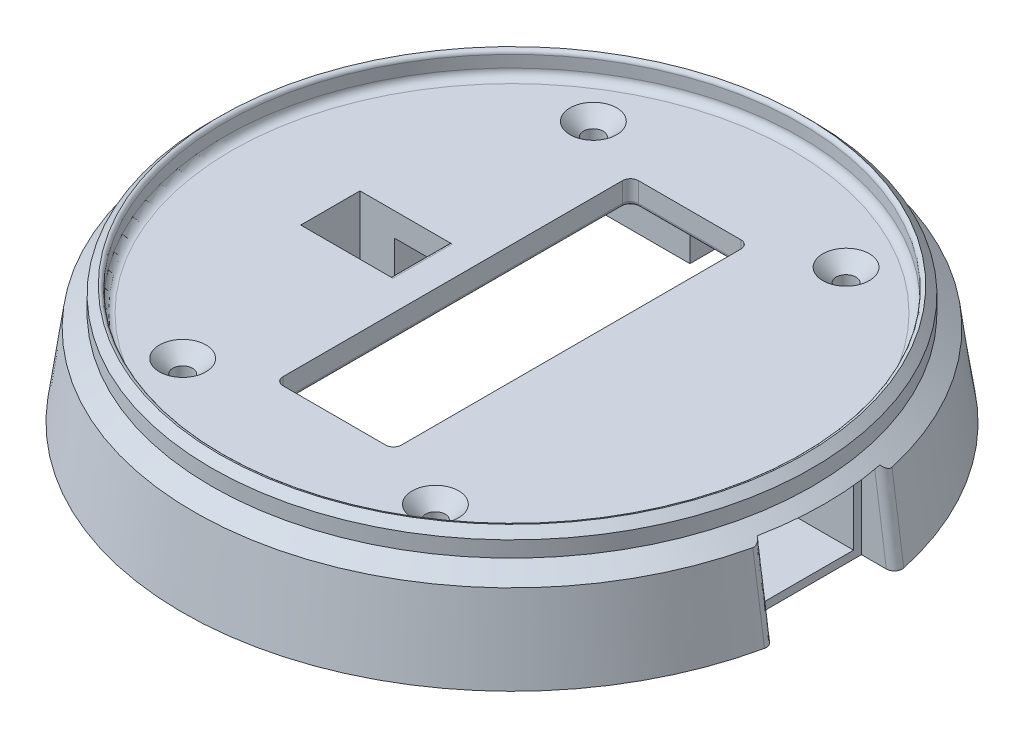
SolidWorks part; units mm, degrees
ref_plane "Front Plane" through (0, 0, 0) normal (0, 0, 1) x (1, 0, 0)
ref_plane "Top Plane" through (0, 0, 0) normal (0, 1, 0) x (1, 0, 0)
ref_plane "Right Plane" through (0, 0, 0) normal (1, 0, 0) x (0, 0, -1)
sketch "Sketch1" plane through (0, 0, 0) normal (0, 1, 0) x (1, 0, 0)
  circle A0 centre (0, 0) radius 41.73
  dimension "D1" = 83.46
extrude "Boss-Extrude1" add sketch "Sketch1" along normal blind 12 draft 8
sketch "Sketch2" plane through (0, 12, 0) normal (0, 1, 0) x (1, 0, 0)
  line L1 (18.65, -28.65) -> (-18.65, -28.65)
  line L2 (18.65, -28.65) -> (18.65, 28.65)
  line L3 (18.65, 28.65) -> (-18.65, 28.65)
  line L4 (-18.65, -28.65) -> (-18.65, 28.65)
  line L5 (18.65, -28.65) -> (-18.65, 28.65) construction
  line L6 (18.65, 28.65) -> (-18.65, -28.65) construction
  point P0 (0, 0)
  dimension "D1" = 37.3
  dimension "D2" = 57.3
extrude "Cut-Extrude1" cut sketch "Sketch2" against normal up to surface (12 mm away) from offset 3 up to face at (0, 0, 41.73) offset against normal yes
sketch "Sketch3" plane through (0, 0, -28.65) normal (0, 0, 1) x (1, 0, 0)
  line L0 (-18.65, 0) -> (18.65, 0) construction
  line L1 (-6.12, 0) -> (6.38, 0)
  line L2 (-6.12, 0) -> (-6.12, 8.5)
  line L3 (-6.12, 8.5) -> (6.38, 8.5)
  line L4 (6.38, 0) -> (6.38, 8.5)
  point P4 (0, 0)
  point P5 (0, 0)
  point P6 (0.13, 8.5)
  dimension "D1" = 12.5
  dimension "D2" = 8.5
  dimension "D3" = 0.13
extrude "Cut-Extrude3" cut sketch "Sketch3" against normal up to surface (12.6288 mm away) up to face at (0, 12, 40.0435)
fillet "Fillet1" radius 2 2 edges at (6.38, 8.5, -34.3401) (-6.12, 8.5, -34.3604)
sketch "Sketch4" plane through (0, 12, 0) normal (0, 1, 0) x (1, 0, 0)
  line L0 (0, 0) -> (0, -22.5) construction
  line L1 (7.5, -22.5) -> (-7.5, -22.5)
  line L2 (7.5, -22.5) -> (7.5, 22.5)
  line L3 (7.5, 22.5) -> (-7.5, 22.5)
  line L4 (-7.5, -22.5) -> (-7.5, 22.5)
  line L5 (0, 0) -> (0, 22.5) construction
  point P4 (0, 0)
  dimension "D1" = 15
  dimension "D2" = 45
extrude "Cut-Extrude4" cut sketch "Sketch4" against normal blind 4.8
fillet "Fillet2" radius 1 4 edges at (7.5, 10.5, -22.5) (-7.5, 10.5, -22.5) (7.5, 10.5, 22.5) (-7.5, 10.5, 22.5)
sketch "Sketch6" plane through (18.65, 0, 0) normal (-1, 0, 0) x (0, 0, 1)
  line L0 (-28.65, 0) -> (28.65, 0) construction
  line L1 (-6.6, 1) -> (6.6, 1)
  line L2 (-6.6, 1) -> (-6.6, 10.2)
  line L3 (-6.6, 10.2) -> (6.6, 10.2)
  line L4 (6.6, 1) -> (6.6, 10.2)
  point P4 (0, 10.2)
  point P7 (0, 0)
  dimension "D1" = 9.2
  dimension "D2" = 13.2
  dimension "D3" = 1
extrude "Cut-Extrude5" cut sketch "Sketch6" against normal up to surface (22.4124 mm away) up to face at (0, 12, 40.0435)
chamfer "Chamfer1" distance 2 angle 70 1 edges at (18.65, 9, 0) first distance on face at (18.65, 9.6, 0)
ref_plane "Plane1" through (41.65, 0, 0) normal (-1, 0, 0) x (0, 0, 1)
sketch "Sketch7" plane through (41.65, 0, 0) normal (-1, 0, 0) x (0, 0, 1)
  line L1 (7.6, 10.7) -> (-7.6, 10.7)
  line L2 (7.6, 10.7) -> (7.6, 0)
  line L3 (7.6, 0) -> (-7.6, 0)
  line L4 (-7.6, 10.7) -> (-7.6, 0)
  line L5 (-41.2788, 0) -> (41.73, 0) construction
  line L7 (-6.6, 1) -> (-6.6, 10.2) construction
  line L8 (6.6, 1) -> (-6.6, 1) construction
  line L9 (-6.6, 1) -> (-6.6, 10.2) construction
  line L10 (6.6, 1) -> (-6.6, 1) construction
  line L11 (6.6, 10.2) -> (-6.6, 10.2)
  line L12 (-6.6, 10.2) -> (-6.6, 1)
  line L13 (-6.6, 1) -> (6.6, 1)
  line L14 (6.6, 1) -> (6.6, 10.2)
  line L15 (6.6, 10.2) -> (-6.6, 10.2) construction
  line L16 (-6.6, 10.2) -> (-6.6, 1) construction
  line L17 (-6.6, 1) -> (6.6, 1) construction
  line L18 (6.6, 1) -> (6.6, 10.2) construction
  point P6 (0, 0)
  point P11 (0, 10.2)
  dimension "D1" = 15.2
  dimension "D2" = 10.7
  dimension "D3" = 0
extrude "Cut-Extrude6" cut sketch "Sketch7" along normal blind 5 and the other way blind 2
fillet "Fillet3" radius 1 3 edges at (40.2262, 10.7, 0)
sketch "Sketch8" plane through (0, 12, 0) normal (0, 1, 0) x (1, 0, 0)
  circle A0 centre (-15.85, 26.15) radius 1.25
  circle A1 centre (-15.85, -25.85) radius 1.25
  circle A2 centre (16.15, 26.15) radius 1.25
  circle A3 centre (16.15, -25.85) radius 1.25
  circle A4 centre (-15.85, 26.15) radius 1.6 construction
  circle A5 centre (16.15, 26.15) radius 1.6 construction
  circle A6 centre (-15.85, -25.85) radius 1.6 construction
  circle A8 centre (16.15, -25.85) radius 1.6 construction
  dimension "D1" = 2.5
extrude "Cut-Extrude7" cut sketch "Sketch8" against normal up to surface (3 mm away) up to face at (0, 9, 0)
chamfer "Chamfer2" distance 1.7 angle 45 4 edges at (16.15, 12, 27.1) (16.15, 12, -24.9) (-15.85, 12, -24.9) (-15.85, 12, 27.1)
chamfer "Chamfer3" distance 1.7 angle 45 1 edges at (0, 12, 40.0435) first distance on face at (11.9078, 5.4482, -20.4422)
sketch "Sketch9" plane through (0, 12, 0) normal (0, 1, 0) x (1, 0, 0)
  circle A0 centre (0, 0) radius 36.5461
  circle A1 centre (0, 0) radius 38.0461
  circle A2 centre (0, 0) radius 38.0461
  dimension "D1" = 0
  dimension "D2" = 1.5
extrude "Boss-Extrude2" add sketch "Sketch9" along normal blind 3
fillet "Fillet4" radius 1 1 edges at (0, 12, 36.5461)
chamfer "Chamfer4" distance 1 angle 45 1 edges at (0, 15, 38.0461)
fillet "Fillet5" radius 0.5 1 edges at (0, 15, 36.5461)
fillet "Fillet6" radius 1 5 edges at (-5.3656, 8.0648, -40.2404) (5.95, 7.739, -40.2045) (0.1307, 8.5, -40.5352)
sketch "Sketch10" plane through (0, 12, 0) normal (0, 1, 0) x (1, 0, 0)
  line L0 (0, 0) -> (-18, 0) construction
  line L2 (-13, 3.75) -> (-23, 3.75)
  line L3 (-13, 3.75) -> (-13, -3.75)
  line L4 (-13, -3.75) -> (-23, -3.75)
  line L5 (-23, 3.75) -> (-23, -3.75)
  line L6 (-13, 3.75) -> (-23, -3.75) construction
  line L7 (-13, -3.75) -> (-23, 3.75) construction
  dimension "D2" = 7.5
  dimension "D1" = 18
  dimension "D3" = 10
extrude "Cut-Extrude8" cut sketch "Sketch10" against normal up to surface (12 mm away) up to face at (12.1341, 0, -11.2414)
chamfer "Chamfer5" distance 4.5 angle 34 1 edges at (-13, 9, 0) first distance on face at (16.15, 9, 27.1)
fillet "Fillet7" radius 0.5 2 edges at (-12.9477, 12, 0) (-8.5, 9, 0)
fillet "Fillet8" radius 0.5 8 edges at (-7.2071, 9, -22.2071) (0, 9, -22.5) (7.2071, 9, -22.2071) (7.5, 9, 0) (7.2071, 9, 22.2071) (0, 9, 22.5) (-7.2071, 9, 22.2071) (-7.5, 9, 0)
